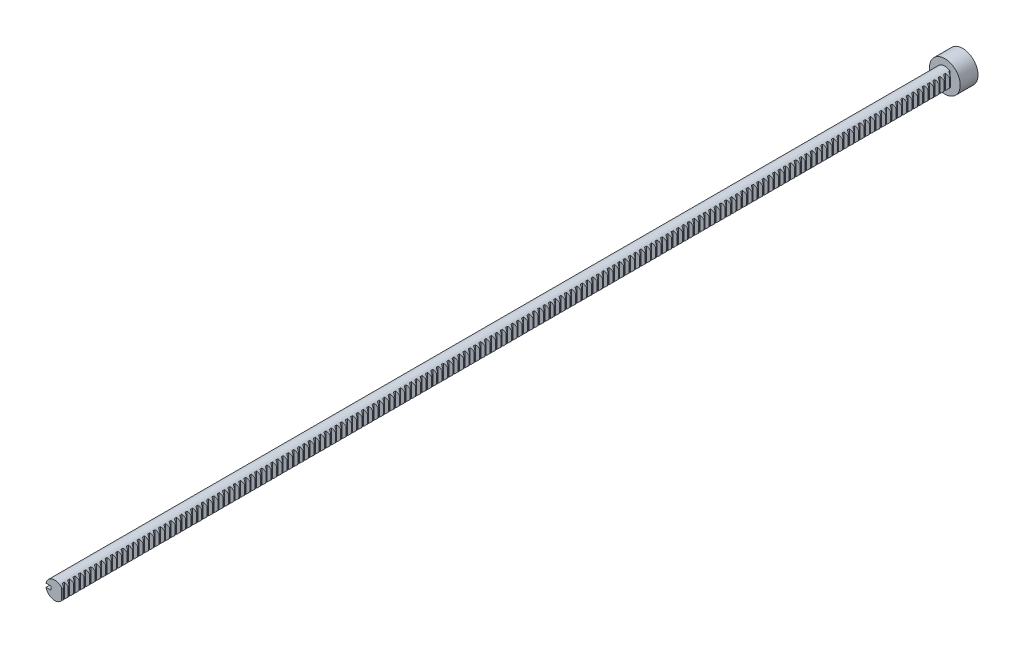
SolidWorks part; units mm, degrees
ref_plane "Front Plane" through (0, 0, 0) normal (0, 0, 1) x (1, 0, 0)
ref_plane "Top Plane" through (0, 0, 0) normal (0, 1, 0) x (1, 0, 0)
ref_plane "Right Plane" through (0, 0, 0) normal (1, 0, 0) x (0, 0, -1)
sketch "Sketch1" plane through (0, 0, 0) normal (0, 0, 1) x (1, 0, 0)
  line L0 (0, 0) -> (0, 40) construction
  line L2 (-2, 41) -> (-4.899, 41)
  line L3 (-2, 41) -> (-2, 39)
  line L4 (-2, 39) -> (-4.899, 39)
  arc A0 (-4.899, 39) -> (-4.899, 41) centre (0, 40) ccw
  dimension "D1" = 10
  dimension "D2" = 40
  dimension "D3" = 2
  dimension "D4" = 2
extrude "Boss-Extrude1" add sketch "Sketch1" along normal mid plane 500
sketch "Sketch2" plane through (0, 0, 0) normal (0, 1, 0) x (1, 0, 0)
  line L0 (2.8184, 250) -> (2.8184, 249.4573)
  line L1 (5, 250) -> (-4.899, 250) construction
  line L2 (2.8184, 249.4573) -> (4.3353, 248.75)
  line L3 (2.8184, 250) -> (7.0945, 250)
  line L4 (2.8184, 250) -> (2.8184, 247) construction
  line L5 (7.0945, 250) -> (7.0945, 247)
  line L6 (7.0945, 247) -> (2.8184, 247)
  line L7 (2.8184, 248.5) -> (4.3353, 248.5) construction
  line L8 (4.3353, 248.75) -> (4.3353, 248.25)
  line L9 (2.8184, 247.5427) -> (4.3353, 248.25)
  line L10 (2.8184, 247) -> (2.8184, 247.5427)
  dimension "D1" = 65
  dimension "D2" = 0.5
  dimension "D3" = 3
extrude "Cut-Extrude3" cut sketch "Sketch2" against normal through all and the other way through all
pattern_linear "LPattern1" count 200 spacing 3 along (0, 0, 1) of "Cut-Extrude3"
sketch "Sketch3" plane through (0, 0, -250) normal (0, 0, -1) x (-1, 0, 0)
  circle A0 centre (0, 40) radius 8.6478
extrude "Boss-Extrude2" add sketch "Sketch3" along normal blind 10
